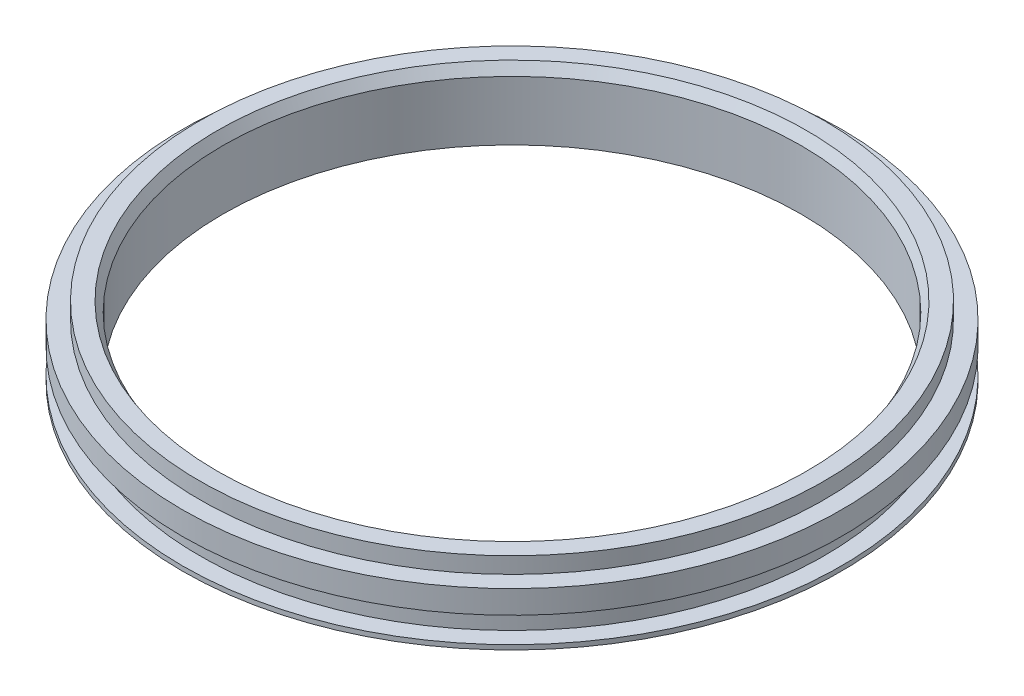
SolidWorks part; units mm, degrees
material "1.4305 (X8CrNiS18-9)"
ref_plane "Front Plane" through (0, 0, 0) normal (0, 0, 1) x (1, 0, 0)
ref_plane "Top Plane" through (0, 0, 0) normal (0, 1, 0) x (1, 0, 0)
ref_plane "Right Plane" through (0, 0, 0) normal (1, 0, 0) x (0, 0, -1)
ref_axis "Axis1" through (0, 4.8, 0) along (0, -1, 0)
sketch "Sketch2" plane through (0, 0, 0) normal (1, 0, 0) x (0, 0, -1)
  line L0 (-27.5, 0) -> (27.5, 0) construction
  line L1 (-27.5, 0) -> (27.5, 0) construction
  line L2 (27, 0) -> (27, 1.1)
  line L3 (27, 1.1) -> (28.5, 1.1)
  line L4 (28.5, 1.1) -> (28.5, 3.1)
  line L8 (27, -1.1) -> (27, 0)
  line L9 (0, 0) -> (0, 17.1848) construction
  line L10 (25, 4.5) -> (-25, 4.5) construction
  line L11 (-25, -1.5) -> (25, -1.5) construction
  line L12 (-25, -1.5) -> (25, -1.5) construction
  line L13 (27, -1.1) -> (28.5, -1.1)
  line L16 (28.5, -1.1) -> (28.5, -1.5)
  line L19 (-27.5, -3.5) -> (27.5, -3.5) construction
  line L20 (-27.5, -3.5) -> (27.5, -3.5) construction
  line L21 (25, 4.5) -> (-25, 4.5) construction
  line L22 (-25, -8) -> (25, -8) construction
  line L23 (-25, -8) -> (25, -8) construction
  line L24 (25, -2) -> (-25, -2) construction
  line L25 (25, -2) -> (-25, -2) construction
  line L26 (25, 4.5) -> (27, 4.5)
  line L30 (28.5, -1.5) -> (25, -1.5)
  line L31 (25, -1.5) -> (25, 4.5)
  line L32 (28.5, 3.1) -> (27, 3.1)
  line L33 (27, 3.1) -> (27, 4.5)
  dimension "D1" = 2.2
  dimension "D2" = 2
  dimension "D3" = 2
  dimension "D5" = 0.5
  dimension "D6" = 1.5
revolve "Revolve1" add sketch "Sketch2" angle 360 about L9
sketch "Sketch3" plane through (0, 0, 0) normal (1, 0, 0) x (0, 0, -1)
  line L0 (25, -2) -> (28.5, -2)
  line L3 (28.5, -2) -> (28.5, -2.4)
  line L4 (28.5, -2.4) -> (27, -2.4)
  line L5 (27, -2.4) -> (27, -4.6)
  line L6 (27, -4.6) -> (28.5, -4.6)
  line L7 (28.5, -4.6) -> (28.5, -6.6)
  line L10 (27, -8) -> (25, -8)
  line L11 (25, -8) -> (25, -2)
  line L12 (-27.5, -3.5) -> (27.5, -3.5) construction
  line L13 (28.5, -1.1) -> (28.5, -1.5) construction
  line L14 (28.5, -6.6) -> (27, -6.6)
  line L15 (27, -6.6) -> (27, -8)
  point P3 (27, -3.5)
  dimension "D1" = 0.5
  dimension "D2" = 2.2
  dimension "D3" = 2
  dimension "D4" = 2
revolve "Revolve2" [suppressed] add sketch "Sketch3" angle 360 about axis through (0, 4.8, 0) along (0, -1, 0)
chamfer "Chamfer1" distance 0.5 angle 60 1 edges at (0, 4.5, -25) first distance on face at (0, 4.5, -25)
chamfer "Chamfer2" [suppressed] distance 0.5 angle 60
